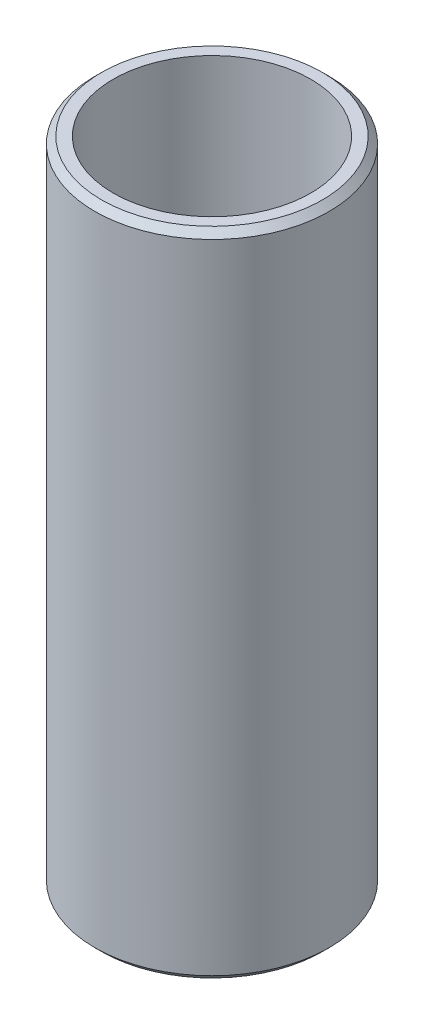
SolidWorks part; units mm, degrees
ref_plane "Front Plane" through (0, 0, 0) normal (0, 0, 1) x (1, 0, 0)
ref_plane "Top Plane" through (0, 0, 0) normal (0, 1, 0) x (1, 0, 0)
ref_plane "Right Plane" through (0, 0, 0) normal (1, 0, 0) x (0, 0, -1)
sketch "Sketch1" plane through (0, 0, 0) normal (0, 1, 0) x (1, 0, 0)
  circle A0 centre (0, 0) radius 57.5
  dimension "SHAFT_OD" = 115
extrude "Boss-Extrude1" add sketch "Sketch1" along normal blind 319.5752
sketch "Sketch2" plane through (0, 0, 0) normal (0, 1, 0) x (1, 0, 0)
  circle A0 centre (0, 0) radius 48.4805
  dimension "BORE_D" = 96.961
extrude "Cut-Extrude1" cut sketch "Sketch2" along normal through all
chamfer "Chamfer1" distance 3.2815 angle 45 2 edges at (0, 319.5752, 57.5) (0, 0, 57.5)
